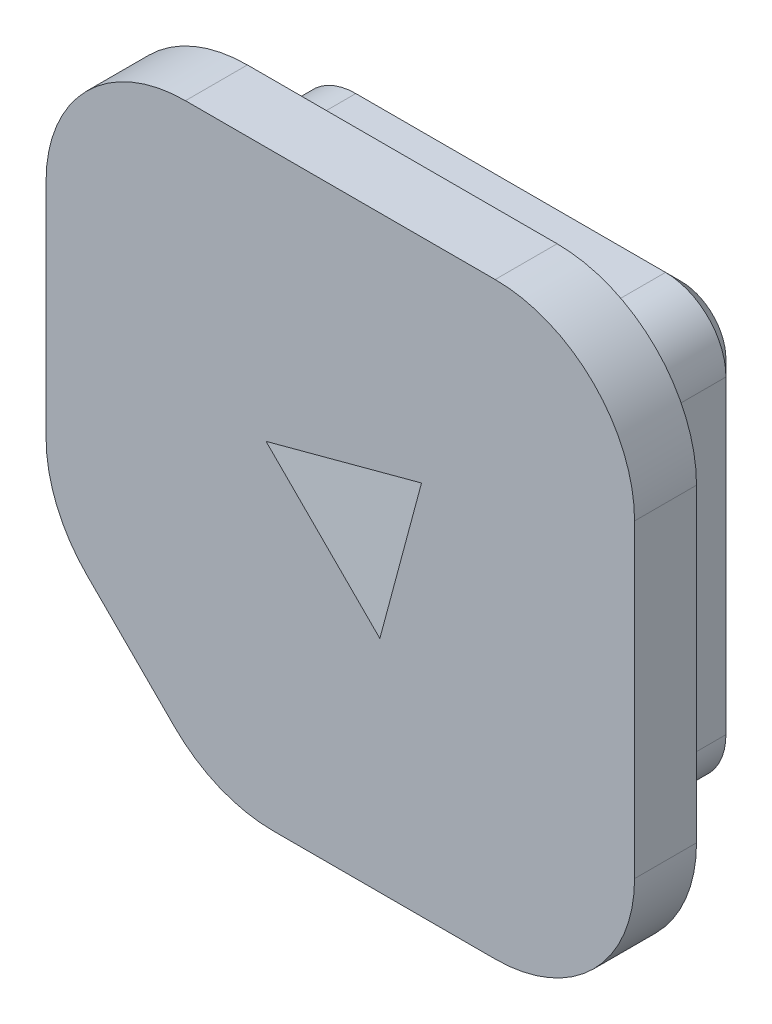
SolidWorks part; units mm, degrees
ref_plane "Front Plane" through (0, 0, 0) normal (0, 0, 1) x (1, 0, 0)
ref_plane "Top Plane" through (0, 0, 0) normal (0, 1, 0) x (1, 0, 0)
ref_plane "Right Plane" through (0, 0, 0) normal (1, 0, 0) x (0, 0, -1)
sketch "Sketch1" plane through (0, 0, 0) normal (0, 0, 1) x (1, 0, 0)
  line L51 (-12.9687, -11.0187) -> (-22.9687, -11.0187)
  line L52 (-11.0187, -22.9687) -> (-11.0187, -12.9687)
  line L53 (-20.1403, -24.9187) -> (-12.9687, -24.9187)
  line L54 (-24.3475, -21.5191) -> (-21.5191, -24.3475)
  line L55 (-24.9187, -12.9687) -> (-24.9187, -20.1403)
  line L56 (-12.9687, -11.0187) -> (-22.9687, -11.0187)
  line L57 (-11.0187, -22.9687) -> (-11.0187, -12.9687)
  line L58 (-20.1403, -24.9187) -> (-12.9687, -24.9187)
  line L59 (-24.3475, -21.5191) -> (-21.5191, -24.3475)
  line L60 (-24.9187, -12.9687) -> (-24.9187, -20.1403)
  arc A52 (-11.0187, -12.9687) -> (-12.9687, -11.0187) centre (-12.9687, -12.9687) ccw
  arc A53 (-12.9687, -24.9187) -> (-11.0187, -22.9687) centre (-12.9687, -22.9687) ccw
  arc A54 (-21.5191, -24.3475) -> (-20.1403, -24.9187) centre (-20.1403, -22.9687) ccw
  arc A55 (-24.9187, -20.1403) -> (-24.3475, -21.5191) centre (-22.9687, -20.1403) ccw
  arc A56 (-22.9687, -11.0187) -> (-24.9187, -12.9687) centre (-22.9687, -12.9687) ccw
  arc A57 (-11.0187, -12.9687) -> (-12.9687, -11.0187) centre (-12.9687, -12.9687) ccw
  arc A58 (-12.9687, -24.9187) -> (-11.0187, -22.9687) centre (-12.9687, -22.9687) ccw
  arc A59 (-21.5191, -24.3475) -> (-20.1403, -24.9187) centre (-20.1403, -22.9687) ccw
  arc A60 (-24.9187, -20.1403) -> (-24.3475, -21.5191) centre (-22.9687, -20.1403) ccw
  arc A61 (-22.9687, -11.0187) -> (-24.9187, -12.9687) centre (-22.9687, -12.9687) ccw
  dimension "D1" = 0.05
sketch "Sketch2" plane through (0, 0, 0) normal (0, 0, 1) x (1, 0, 0)
  line L67 (-26.1507, -23.3222) -> (-23.3222, -26.1507)
  line L68 (-20.1403, -27.4687) -> (-12.9687, -27.4687)
  line L69 (-8.4687, -22.9687) -> (-8.4687, -12.9687)
  line L70 (-12.9687, -8.4687) -> (-22.9687, -8.4687)
  line L71 (-27.4687, -12.9687) -> (-27.4687, -20.1403)
  line L72 (-26.1507, -23.3222) -> (-23.3222, -26.1507)
  line L73 (-20.1403, -27.4687) -> (-12.9687, -27.4687)
  line L74 (-8.4687, -22.9687) -> (-8.4687, -12.9687)
  line L75 (-12.9687, -8.4687) -> (-22.9687, -8.4687)
  line L76 (-27.4687, -12.9687) -> (-27.4687, -20.1403)
  arc A66 (-27.4687, -20.1403) -> (-26.1507, -23.3222) centre (-22.9687, -20.1403) ccw
  arc A67 (-23.3222, -26.1507) -> (-20.1403, -27.4687) centre (-20.1403, -22.9687) ccw
  arc A68 (-12.9687, -27.4687) -> (-8.4687, -22.9687) centre (-12.9687, -22.9687) ccw
  arc A69 (-8.4687, -12.9687) -> (-12.9687, -8.4687) centre (-12.9687, -12.9687) ccw
  arc A70 (-22.9687, -8.4687) -> (-27.4687, -12.9687) centre (-22.9687, -12.9687) ccw
  arc A71 (-27.4687, -20.1403) -> (-26.1507, -23.3222) centre (-22.9687, -20.1403) ccw
  arc A72 (-23.3222, -26.1507) -> (-20.1403, -27.4687) centre (-20.1403, -22.9687) ccw
  arc A73 (-12.9687, -27.4687) -> (-8.4687, -22.9687) centre (-12.9687, -22.9687) ccw
  arc A74 (-8.4687, -12.9687) -> (-12.9687, -8.4687) centre (-12.9687, -12.9687) ccw
  arc A75 (-22.9687, -8.4687) -> (-27.4687, -12.9687) centre (-22.9687, -12.9687) ccw
  dimension "D1" = 2.5
sketch "Sketch3" plane through (0, 0, 0) normal (0, 0, 1) x (1, 0, 0)
  line L0 (-21.6518, -14.2856) -> (-13.8206, -13.8206)
  line L1 (-17.75, -80) -> (-22.5, 0) construction
  line L2 (-17.75, -80) -> (-13, 0) construction
  line L3 (-13.8206, -13.8206) -> (-14.2856, -21.6518)
  line L4 (0, -22.5) -> (-80, -17.75) construction
  line L5 (-14.2856, -21.6518) -> (-21.2389, -21.2389)
  line L6 (-21.2389, -21.2389) -> (-21.6518, -14.2856)
  line L7 (-80, -17.75) -> (0, -13) construction
extrude "Boss-Extrude1" add sketch "Sketch2" along normal blind 2
extrude "Boss-Extrude2" add sketch "Sketch1" against normal blind 4
extrude "Cut-Extrude1" [suppressed] cut sketch "Sketch3" along normal through all both and the other way through all
sketch "Sketch4" plane through (0, 0, 2) normal (0, 0, 1) x (1, 0, 0)
  line L0 (-26.1507, -23.3222) -> (-23.3222, -26.1507) construction
  line L1 (-16.6922, -20.3665) -> (-15.3474, -15.3474)
  line L2 (-15.3474, -15.3474) -> (-20.3665, -16.6922)
  line L3 (-20.3665, -16.6922) -> (-16.6922, -20.3665)
  line L4 (-12.9687, -8.4687) -> (-22.9687, -8.4687) construction
  line L5 (-8.4687, -22.9687) -> (-8.4687, -12.9687) construction
  circle A0 centre (-17.4687, -17.4687) radius 1.5 construction
  dimension "D1" = 3
  dimension "D2" = 9
  dimension "D3" = 9
extrude "Cut-Extrude2" cut sketch "Sketch4" against normal through all
chamfer "Chamfer1" distance 0.5 angle 45 13 edges at (-24.7702, -20.8865, -4) (-22.9333, -22.9333, -4) (-24.9187, -16.5545, -4) (-20.8865, -24.7702, -4) (-24.3475, -11.5898, -4) (-16.5545, -24.9187, -4) (-17.9687, -11.0187, -4) (-11.5898, -24.3475, -4) (-11.5898, -11.5898, -4) (-11.0187, -17.9687, -4) (-16.0198, -17.8569, -4) (-18.5293, -18.5293, -4) (-17.8569, -16.0198, -4)
